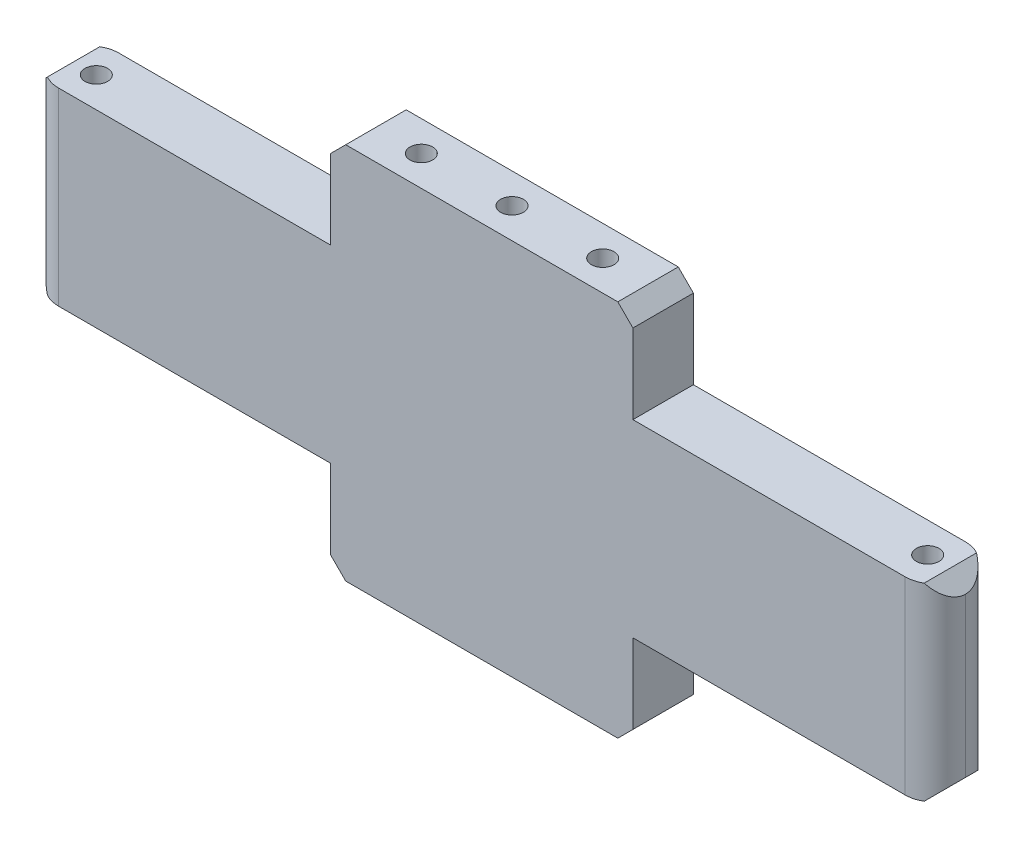
SolidWorks part; units mm, degrees
ref_plane "前视基准面" through (0, 0, 0) normal (0, 0, 1) x (1, 0, 0)
ref_plane "上视基准面" through (0, 0, 0) normal (0, 1, 0) x (1, 0, 0)
ref_plane "右视基准面" through (0, 0, 0) normal (1, 0, 0) x (0, 0, -1)
other "Configuration Table"
sketch "草图1" plane through (0, 0, 0) normal (0, 0, 1) x (1, 0, 0)
  line L1 (-20, 25) -> (20, 25)
  line L2 (-20, 25) -> (-20, 12.5)
  line L3 (-20, -25) -> (20, -25)
  line L4 (20, 25) -> (20, 12.5)
  line L5 (-20, 25) -> (20, -25) construction
  line L6 (-20, -25) -> (20, 25) construction
  line L7 (-20, 12.5) -> (-60, 12.5)
  line L8 (-60, 12.5) -> (-60, -12.5)
  line L9 (-60, -12.5) -> (-20, -12.5)
  line L10 (-20, -12.5) -> (-20, -25)
  line L11 (0, 25) -> (0, -25) construction
  line L12 (60, -12.5) -> (20, -12.5)
  line L13 (60, 12.5) -> (60, -12.5)
  line L14 (20, 12.5) -> (60, 12.5)
  line L15 (20, -12.5) -> (20, -25)
  point P0 (0, 0)
  dimension "D1" = 40
  dimension "D2" = 50
  dimension "D3" = 12.5
  dimension "D4" = 12.5
  dimension "D5" = 40
extrude "凸台-拉伸1" add sketch "草图1" along normal blind 8
sketch "草图2" plane through (0, 0, 0) normal (0, 0, -1) x (-1, 0, 0)
  circle A0 centre (0, 0) radius 15
  dimension "D1" = 30
extrude "切除-拉伸1" [suppressed] cut sketch "草图2" against normal blind 4
sketch "草图3" [suppressed] plane through (0, 0, 4) normal (0, 0, -1) x (-1, 0, 0)
  circle A0 centre (0, 11) radius 2
  circle A1 centre (9.5263, 5.5) radius 2
  circle A2 centre (9.5263, -5.5) radius 2
  circle A3 centre (0, -11) radius 2
  circle A4 centre (-9.5263, -5.5) radius 2
  circle A5 centre (-9.5263, 5.5) radius 2
  point P15 (0, 0)
  dimension "D1" = 4
  dimension "D2" = 11
  dimension "D3" = 6
extrude "切除-拉伸2" [suppressed] cut sketch "草图3" against normal blind 10
chamfer "倒角1" distance 2 angle 45 4 edges at (-20, 25, 4) (20, 25, 4) (20, -25, 4) (-20, -25, 4)
sketch "草图4" plane through (0, 25, 0) normal (0, 1, 0) x (1, 0, 0)
  line L0 (18, 0) -> (-18, 0) construction
  line L1 (-20, -8) -> (-20, 0) construction
  circle A0 centre (-12, -4) radius 1.5
  circle A1 centre (0, -4) radius 1.5
  circle A2 centre (12, -4) radius 1.5
  dimension "D1" = 3
  dimension "D2" = 4
  dimension "D3" = 8
  dimension "D6" = 12
  dimension "D7" = 12
  dimension "D4" = 2
  dimension "D5" = 2
extrude "切除-拉伸3" cut sketch "草图4" against normal blind 50
sketch "草图5" plane through (0, -25, 0) normal (0, -1, 0) x (1, 0, 0)
  line L0 (-18, 8) -> (18, 8) construction
  line L2 (-20, 0) -> (-20, 8) construction
  circle A0 centre (-14, 4) radius 1.5
  circle A1 centre (0, 4) radius 1.5
  circle A2 centre (14, 4) radius 1.5
  dimension "D1" = 3
  dimension "D2" = 4
  dimension "D3" = 6
  dimension "D6" = 14
  dimension "D7" = 14
  dimension "D4" = 2
  dimension "D5" = 2
extrude "切除-拉伸4" [suppressed] cut sketch "草图5" against normal blind 6
chamfer "倒角3" distance 2 angle 45 4 edges at (60, 12.5, 4) (60, -12.5, 4) (-60, 12.5, 4) (-60, -12.5, 4)
fillet "圆角1" radius 4 4 edges at (60, 0, 0) (60, 0, 8) (-60, 0, 0) (-60, 0, 8)
sketch "草图6" plane through (0, 12.5, 0) normal (0, 1, 0) x (1, 0, 0)
  line L0 (20, -4) -> (60, -4) construction
  line L1 (20, 0) -> (20, -8) construction
  line L2 (20, -8) -> (20, 0) construction
  circle A0 centre (55, -4) radius 1.5
  dimension "D2" = 3
  dimension "D1" = 35
extrude "切除-拉伸5" cut sketch "草图6" against normal through all
ref_plane "基准面2" through (0, 0, 0) normal (1, 0, 0) x (0, 0, -1)
mirror "镜向4" about plane through (0, 0, 0) normal (1, 0, 0) of face at (53.5, 12.5, 4)
chamfer "倒角2" [suppressed] distance 0.5 angle 45
ref_plane "基准面1" through (0, 0, 0) normal (1, 0, 0) x (0, 0, -1)
